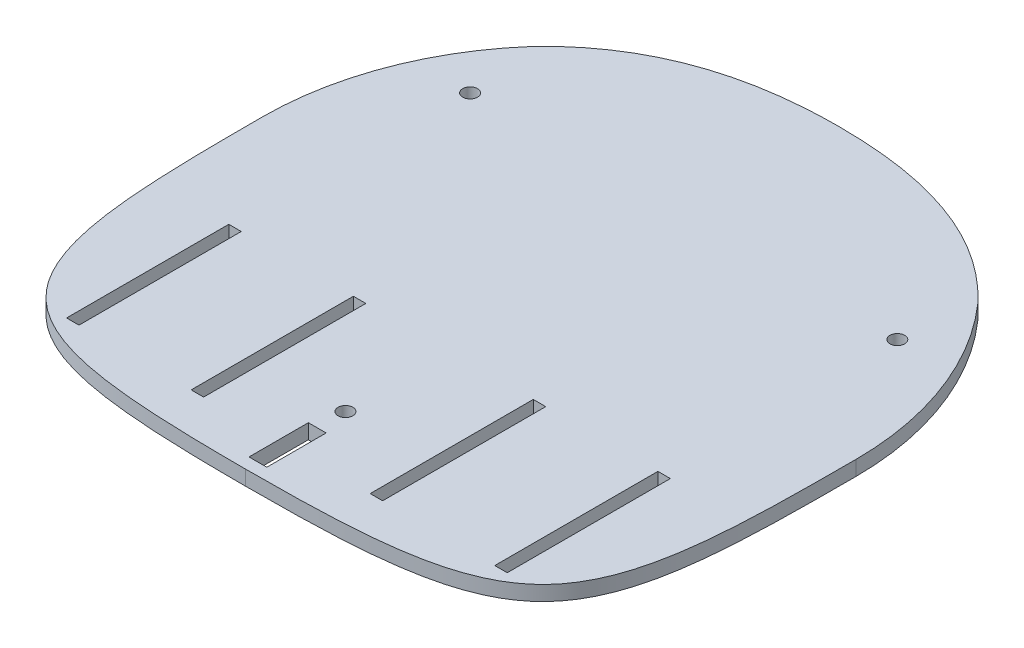
SolidWorks part; units mm, degrees
ref_plane "Front Plane" through (0, 0, 0) normal (0, 0, 1) x (1, 0, 0)
ref_plane "Top Plane" through (0, 0, 0) normal (0, 1, 0) x (1, 0, 0)
ref_plane "Right Plane" through (0, 0, 0) normal (1, 0, 0) x (0, 0, -1)
sketch "Layer1Limits" plane through (0, 0, 0) normal (0, 1, 0) x (1, 0, 0)
  line L0 (-127, 119.8228) -> (127, -134.1772) construction
  line L1 (-127, -134.1772) -> (127, -134.1772) construction
  line L2 (-127, -134.1772) -> (-127, 119.8228) construction
  line L3 (-127, 119.8228) -> (127, 119.8228) construction
  line L4 (127, -134.1772) -> (127, 119.8228) construction
  line L5 (127, 119.8228) -> (-127, -134.1772) construction
  line L6 (0, -1000) -> (0, 49000) construction
  point P4 (0, -7.1772)
  dimension "D1" = 254
  dimension "D2" = 254
sketch "Sketch1" plane through (0, 0, 0) normal (0, 1, 0) x (1, 0, 0)
  line L0 (0, 0) -> (-157.9039, -157.9039) construction
  line L1 (0, -134.1772) -> (0, 127) construction
  line L2 (-127, -134.1772) -> (127, -134.1772) construction
  arc A0 (127, 0) -> (-127, 0) centre (0, 0) ccw
  spline S0 degree 3 poles (-127, 0) (-127, -50.6247) (-125.8471, -127.4032) (-59.0891, -134.1772) (0, -134.1772) knots 0 0 0 0 0.496988 1 1 1 1
  spline S1 degree 3 poles (127, 0) (127, -50.6247) (125.8471, -127.4032) (59.0891, -134.1772) (0, -134.1772) knots 0 0 0 0 0.496988 1 1 1 1
  dimension "D1" = 254
extrude "Base" add sketch "Sketch1" along normal blind 6.35
sketch "Sketch16" plane through (0, 6.35, 0) normal (0, 1, 0) x (1, 0, 0)
  line L0 (0, -1000) -> (0, 49000) construction
  line L1 (-95.2696, 133.35) -> (-95.2696, 83.9803)
  line L2 (-95.2696, 133.35) -> (95.2696, 133.35)
  line L3 (95.2696, 133.35) -> (95.2696, 83.9803)
  arc A0 (127, 0) -> (-127, 0) centre (0, 0) ccw construction
  spline S0 degree 3 poles (-95.2696, 83.9803) (-69.156, 111.7112) (-34.9729, 119.8228) (0, 119.8228) knots 0 0 0 0 1 1 1 1
  spline S1 degree 3 poles (95.2696, 83.9803) (69.156, 111.7112) (34.9729, 119.8228) (0, 119.8228) knots 0 0 0 0 1 1 1 1
extrude "EmptySpaceTrim" cut sketch "Sketch16" against normal through all
sketch "ShaftLayout" plane through (0, 6.35, 0) normal (0, 1, 0) x (1, 0, 0)
  line L0 (-127, 0) -> (127, 0) construction
  line L1 (0, 133.35) -> (0, -127) construction
  line L2 (-114.7053, -6.35) -> (-104.7993, -6.35)
  line L3 (-36.3853, -38) -> (-94.3853, -38)
  line L4 (-36.3853, -38) -> (-36.3853, 38)
  line L5 (-36.3853, 38) -> (-94.3853, 38)
  line L6 (-94.3853, -38) -> (-94.3853, 38)
  line L7 (-36.3853, -38) -> (-94.3853, 38) construction
  line L8 (-36.3853, 38) -> (-94.3853, -38) construction
  line L9 (-102.0053, -15.875) -> (-104.7993, -15.875)
  line L10 (-102.0053, -15.875) -> (-102.0053, 15.875)
  line L11 (-102.0053, 15.875) -> (-104.7993, 15.875)
  line L12 (-104.7993, -15.875) -> (-104.7993, 15.875)
  line L13 (-102.0053, -15.875) -> (-104.7993, 15.875) construction
  line L14 (-102.0053, 15.875) -> (-104.7993, -15.875) construction
  line L15 (-114.7053, -6.35) -> (-114.7053, 6.35)
  line L16 (-104.7993, -6.35) -> (-104.7993, 6.35)
  line L17 (-114.7053, 6.35) -> (-104.7993, 6.35)
  line L18 (-114.7053, -6.35) -> (-104.7993, 6.35) construction
  line L19 (-104.7993, -6.35) -> (-114.7053, 6.35) construction
  line L20 (-116.2928, -9.525) -> (-114.7053, -9.525)
  line L21 (-116.2928, -9.525) -> (-116.2928, 9.525)
  line L22 (-114.7053, -9.525) -> (-114.7053, 9.525)
  line L23 (-116.2928, 9.525) -> (-114.7053, 9.525)
  line L24 (-116.2928, -9.525) -> (-114.7053, 9.525) construction
  line L25 (-114.7053, -9.525) -> (-116.2928, 9.525) construction
  line L26 (-127.4053, -7.9375) -> (-116.2928, -7.9375)
  line L27 (-127.4053, -7.9375) -> (-127.4053, 7.9375)
  line L28 (-116.2928, -7.9375) -> (-116.2928, 7.9375)
  line L29 (-127.4053, 7.9375) -> (-116.2928, 7.9375)
  line L30 (-127.4053, -7.9375) -> (-116.2928, 7.9375) construction
  line L31 (-116.2928, -7.9375) -> (-127.4053, 7.9375) construction
  line L32 (-17.3353, -7.9375) -> (-28.4478, -7.9375)
  line L33 (-30.0353, -9.525) -> (-28.4478, -9.525)
  line L34 (-30.0353, -9.525) -> (-30.0353, 9.525)
  line L35 (-30.0353, 9.525) -> (-28.4478, 9.525)
  line L36 (-28.4478, -9.525) -> (-28.4478, 9.525)
  line L37 (-30.0353, -9.525) -> (-28.4478, 9.525) construction
  line L38 (-30.0353, 9.525) -> (-28.4478, -9.525) construction
  line L39 (-17.3353, -7.9375) -> (-17.3353, 7.9375)
  line L40 (-28.4478, -7.9375) -> (-28.4478, 7.9375)
  line L41 (-17.3353, 7.9375) -> (-28.4478, 7.9375)
  line L42 (-17.3353, -7.9375) -> (-28.4478, 7.9375) construction
  line L43 (-28.4478, -7.9375) -> (-17.3353, 7.9375) construction
  line L45 (-67.3853, -10.033) -> (-56.3853, -10.033)
  line L46 (-67.3853, -10.033) -> (-67.3853, 10.033)
  line L47 (-67.3853, 10.033) -> (-56.3853, 10.033)
  line L48 (-56.3853, -10.033) -> (-56.3853, 10.033)
  line L49 (-67.3853, -10.033) -> (-56.3853, 10.033) construction
  line L50 (-67.3853, 10.033) -> (-56.3853, -10.033) construction
  point P10 (-65.3853, 0)
  point P15 (-103.4023, 0)
  point P20 (-29.2416, 0)
  point P21 (-109.7523, 0)
  point P22 (-115.4991, 0)
  point P23 (-121.8491, 0)
  point P40 (-61.8853, 0)
  point P41 (-22.8916, 0)
  point P50 (0, 0)
  dimension "D1" = 58
  dimension "D2" = 76
  dimension "D3" = 7.62
  dimension "D4" = 2.794
  dimension "D5" = 31.75
  dimension "D6" = 9.906
  dimension "D7" = 12.7
  dimension "D8" = 19.05
  dimension "D9" = 1.5875
  dimension "D10" = 12.7
  dimension "D11" = 15.875
  dimension "D12" = 19.05
  dimension "D13" = 1.5875
  dimension "D14" = 15.875
  dimension "D15" = 12.7
  dimension "D16" = 6.35
  dimension "D17" = 20.066
  dimension "D18" = 20
  dimension "D19" = 11
sketch "MotorLayout" plane through (0, 6.35, 0) normal (0, 1, 0) x (1, 0, 0)
  line L0 (-94.3853, -81.74) -> (-114.3853, -81.74) construction
  line L1 (-94.3853, -110.24) -> (-18.3853, -110.24)
  line L2 (-94.3853, -110.24) -> (-94.3853, -53.24)
  line L3 (-94.3853, -53.24) -> (-18.3853, -53.24)
  line L4 (-18.3853, -110.24) -> (-18.3853, -53.24)
  line L5 (-94.3853, -110.24) -> (-18.3853, -53.24) construction
  line L6 (-94.3853, -53.24) -> (-18.3853, -110.24) construction
  line L7 (-114.7053, -92.0587) -> (-104.7993, -92.0587)
  line L8 (-104.7993, -97.615) -> (-102.0053, -97.615)
  line L9 (-104.7993, -97.615) -> (-104.7993, -65.865)
  line L10 (-104.7993, -65.865) -> (-102.0053, -65.865)
  line L11 (-102.0053, -97.615) -> (-102.0053, -65.865)
  line L12 (-104.7993, -97.615) -> (-102.0053, -65.865) construction
  line L13 (-104.7993, -65.865) -> (-102.0053, -97.615) construction
  line L14 (-36.3853, -38) -> (-94.3853, -38) construction
  line L15 (-114.7053, -92.0587) -> (-114.7053, -71.4212)
  line L16 (-104.7993, -92.0587) -> (-104.7993, -71.4212)
  line L17 (-114.7053, -71.4212) -> (-104.7993, -71.4212)
  line L18 (-114.7053, -92.0587) -> (-104.7993, -71.4212) construction
  line L19 (-104.7993, -92.0587) -> (-114.7053, -71.4212) construction
  line L20 (-103.4023, -1000) -> (-103.4023, 49000) construction
  line L21 (-34.8953, -53.24) -> (-34.8953, -110.24) construction
  point P0 (-56.3853, -81.74)
  point P7 (-103.4023, -81.74)
  point P14 (-109.7523, -81.74)
  dimension "D1" = 20
  dimension "D2" = 76
  dimension "D3" = 57
  dimension "D4" = 2.794
  dimension "D5" = 15.24
  dimension "D6" = 31.75
  dimension "D7" = 20.6375
  dimension "D8" = 12.7
  dimension "D9" = 7.62
  dimension "D10" = 16.51
sketch "Sketch8" plane through (0, 6.35, 0) normal (0, 1, 0) x (1, 0, 0)
  line L0 (-94.3853, -81.74) -> (-18.3853, -81.74) construction
  line L1 (-18.3853, -110.24) -> (-18.3853, -53.24) construction
  line L2 (-94.3853, -53.24) -> (-18.3853, -53.24) construction
  line L3 (-35.7113, -116.463) -> (-41.0453, -116.463)
  line L4 (-35.7113, -116.463) -> (-35.7113, -47.017)
  line L5 (-35.7113, -47.017) -> (-41.0453, -47.017)
  line L6 (-41.0453, -116.463) -> (-41.0453, -47.017)
  line L7 (-35.7113, -116.463) -> (-41.0453, -47.017) construction
  line L8 (-35.7113, -47.017) -> (-41.0453, -116.463) construction
  line L9 (0, -1000) -> (0, 49000) construction
  line L10 (-94.3853, -110.24) -> (-18.3853, -110.24) construction
  line L11 (-3.81, -128.9302) -> (3.81, -128.9302)
  line L12 (89.0513, -46.763) -> (94.3853, -116.59) construction
  line L13 (89.0513, -116.59) -> (94.3853, -46.763) construction
  line L14 (35.7113, -46.763) -> (41.0453, -116.59) construction
  line L15 (-89.0513, -116.463) -> (-94.3853, -116.463)
  line L16 (-89.0513, -116.463) -> (-89.0513, -47.017)
  line L17 (-89.0513, -47.017) -> (-94.3853, -47.017)
  line L18 (-94.3853, -116.463) -> (-94.3853, -47.017)
  line L19 (-89.0513, -116.463) -> (-94.3853, -47.017) construction
  line L20 (-89.0513, -47.017) -> (-94.3853, -116.463) construction
  line L21 (-94.3853, -110.24) -> (-94.3853, -53.24) construction
  line L22 (-3.81, -128.9302) -> (-3.81, -103.5302)
  line L23 (35.7113, -116.59) -> (41.0453, -46.763) construction
  line L24 (-3.81, -103.5302) -> (3.81, -103.5302)
  line L25 (3.81, -128.9302) -> (3.81, -103.5302)
  line L26 (-3.81, -128.9302) -> (3.81, -103.5302) construction
  line L27 (-3.81, -103.5302) -> (3.81, -128.9302) construction
  line L29 (94.3853, -116.59) -> (94.3853, -46.763)
  line L30 (89.0513, -46.763) -> (94.3853, -46.763)
  line L31 (89.0513, -116.59) -> (89.0513, -46.763)
  line L32 (89.0513, -116.59) -> (94.3853, -116.59)
  line L33 (41.0453, -116.59) -> (41.0453, -46.763)
  line L34 (35.7113, -46.763) -> (41.0453, -46.763)
  line L35 (35.7113, -116.59) -> (35.7113, -46.763)
  line L36 (35.7113, -116.59) -> (41.0453, -116.59)
  point P6 (-63.7079, -81.74)
  point P7 (-38.2513, -81.74)
  point P16 (0, -116.2302)
  point P19 (-91.5913, -81.74)
  point P39 (91.5913, -81.74)
  point P40 (38.2513, -81.74)
  dimension "D1" = 5.334
  dimension "D2" = 6.223
  dimension "D4" = 7.62
  dimension "D5" = 25.4
  dimension "D6" = 6.223
  dimension "D3" = 2
extrude "MotorCut" cut sketch "Sketch8" against normal through all
sketch "Sketch11" plane through (0, 6.35, 0) normal (0, 1, 0) x (1, 0, 0)
  line L0 (0, -1000) -> (0, 49000) construction
  line L1 (-127, 0) -> (127, 0) construction
  circle A1 centre (0, -91.44) radius 3.175
  circle A2 centre (-91.44, 53.34) radius 3.175
  circle A3 centre (91.44, 53.34) radius 3.175
  dimension "D1" = 6.35
  dimension "D2" = 91.44
  dimension "D3" = 6.35
  dimension "D6" = 91.44
  dimension "D4" = 53.34
extrude "ScrewCut" cut sketch "Sketch11" against normal through all
